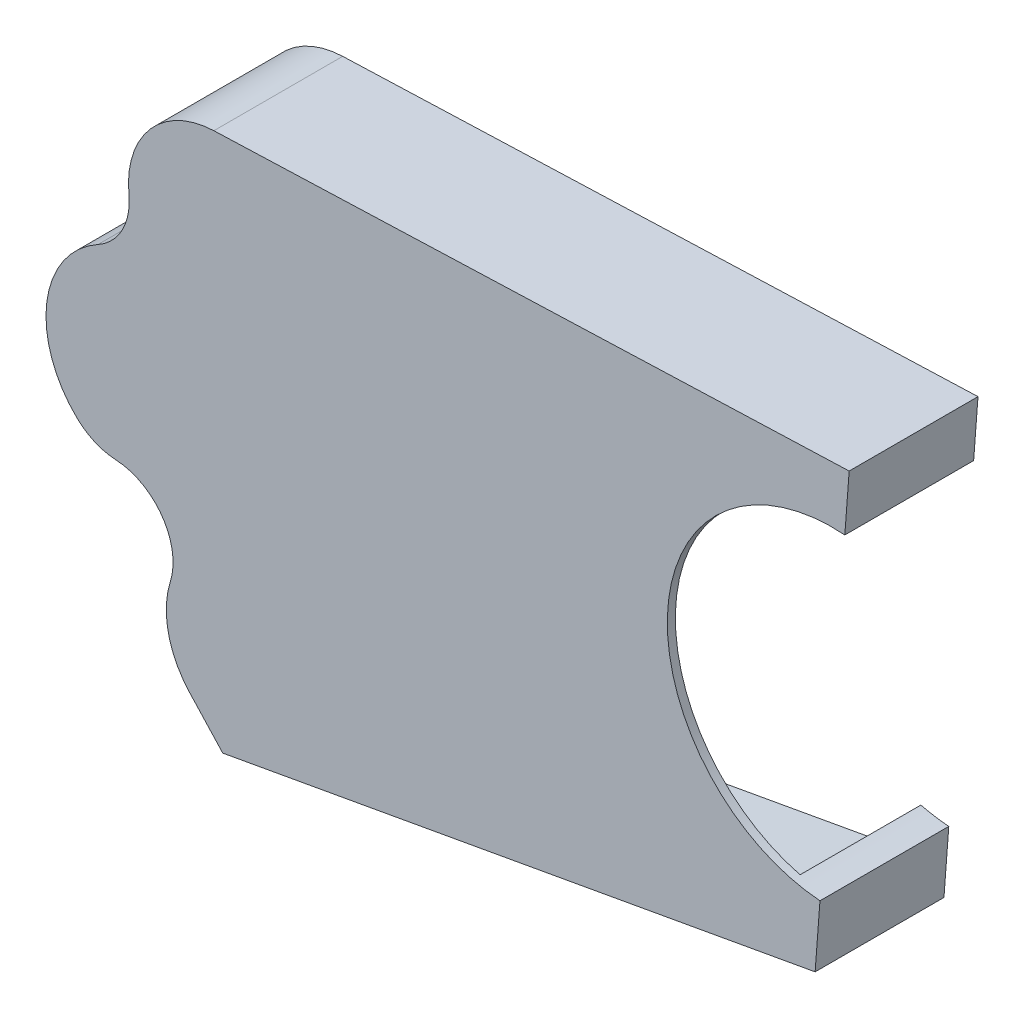
SolidWorks part; units mm, degrees
ref_plane "Front Plane" through (0, 0, 0) normal (0, 0, 1) x (1, 0, 0)
ref_plane "Top Plane" through (0, 0, 0) normal (0, 1, 0) x (1, 0, 0)
ref_plane "Right Plane" through (0, 0, 0) normal (1, 0, 0) x (0, 0, -1)
sketch "Sketch1" plane through (0, 0, 0) normal (0, 0, 1) x (1, 0, 0)
  line L8 (-119.5948, -74.4106) -> (-92.5405, -103.7404)
  line L9 (-119.5948, -74.4106) -> (-92.5405, -103.7404)
  line L10 (-71.3446, -104.5958) -> (-37.2211, -73.1197)
  line L11 (-71.3446, -104.5958) -> (-37.2211, -73.1197)
  line L16 (-27.1401, -68.1042) -> (68.9251, -50.7959)
  line L17 (-111.4072, -83.2869) -> (68.9251, -50.7959)
  line L18 (56.0883, 55.6165) -> (-113.6124, 49.4857)
  line L19 (56.0883, 55.6165) -> (-113.6124, 49.4857)
  line L20 (-114.4495, -69.6645) -> (-87.3952, -98.9943)
  line L21 (-114.4495, -69.6645) -> (-87.3952, -98.9943)
  line L22 (-76.0907, -99.4505) -> (-41.9673, -67.9744)
  line L23 (-76.0907, -99.4505) -> (-41.9673, -67.9744)
  line L28 (-28.3813, -61.2151) -> (67.6838, -43.9068)
  line L29 (-108.8671, -75.7165) -> (67.6838, -43.9068)
  line L30 (56.341, 48.621) -> (-113.3597, 42.4902)
  line L31 (56.341, 48.621) -> (-113.3597, 42.4902)
  line L32 (44.1846, 55.1864) -> (35.7309, -56.7765)
  line L33 (-27.1401, -68.1042) -> (68.9251, -50.7959) construction
  line L34 (-113.6124, 49.4857) -> (56.0883, 55.6165) construction
  line L35 (-111.6252, 43.3) -> (42.409, 31.6699) construction
  line L36 (36.6151, 47.9084) -> (29.1586, -50.848)
  arc A22 (-124.4228, -52.9336) -> (-137.9704, -33.4802) centre (-138.7403, -48.4604) ccw
  arc A23 (-124.4228, -52.9336) -> (-137.9704, -33.4802) centre (-138.7403, -48.4604) ccw
  arc A24 (-124.4228, -52.9336) -> (-119.5948, -74.4106) centre (-103.4238, -59.4942) ccw
  arc A25 (-124.4228, -52.9336) -> (-119.5948, -74.4106) centre (-103.4238, -59.4942) ccw
  arc A26 (-92.5405, -103.7404) -> (-71.3446, -104.5958) centre (-81.5148, -93.5701) ccw
  arc A27 (-92.5405, -103.7404) -> (-71.3446, -104.5958) centre (-81.5148, -93.5701) ccw
  arc A28 (-27.1401, -68.1042) -> (-37.2211, -73.1197) centre (-23.5699, -87.9191) ccw
  arc A29 (-27.1401, -68.1042) -> (-37.2211, -73.1197) centre (-23.5699, -87.9191) ccw
  arc A30 (68.9251, -50.7959) -> (91, -33.5) centre (63.6055, -21.2712) ccw
  arc A31 (68.9251, -50.7959) -> (91, -33.5) centre (63.6055, -21.2712) ccw
  arc A32 (91, -33.5) -> (80.2612, 44.7896) centre (22.6589, -2.9929) ccw
  arc A44 (91, -33.5) -> (80.2612, 44.7896) centre (22.6589, -2.9929) ccw
  arc A45 (80.2612, 44.7896) -> (56.0883, 55.6165) centre (57.1714, 25.636) ccw
  arc A46 (80.2612, 44.7896) -> (56.0883, 55.6165) centre (57.1714, 25.636) ccw
  arc A47 (-113.6124, 49.4857) -> (-134.7058, 25.2795) centre (-112.8181, 27.5) ccw
  arc A48 (-113.6124, 49.4857) -> (-134.7058, 25.2795) centre (-112.8181, 27.5) ccw
  arc A49 (-142.3827, 10.6321) -> (-134.7058, 25.2795) centre (-149.6292, 23.7656) ccw
  arc A50 (-142.3827, 10.6321) -> (-134.7058, 25.2795) centre (-149.6292, 23.7656) ccw
  arc A51 (-142.3827, 10.6321) -> (-147.5429, -29.3643) centre (-130.3054, -11.2571) ccw
  arc A52 (-142.3827, 10.6321) -> (-147.5429, -29.3643) centre (-130.3054, -11.2571) ccw
  arc A53 (-147.5429, -29.3643) -> (-137.9704, -33.4802) centre (-137.2004, -18.5) ccw
  arc A54 (-147.5429, -29.3643) -> (-137.9704, -33.4802) centre (-137.2004, -18.5) ccw
  arc A55 (-117.7413, -55.0211) -> (-137.611, -26.4895) centre (-138.7403, -48.4604) ccw
  arc A56 (-117.7413, -55.0211) -> (-137.611, -26.4895) centre (-138.7403, -48.4604) ccw
  arc A57 (-117.7413, -55.0211) -> (-114.4495, -69.6645) centre (-103.4238, -59.4942) ccw
  arc A58 (-117.7413, -55.0211) -> (-114.4495, -69.6645) centre (-103.4238, -59.4942) ccw
  arc A59 (-87.3952, -98.9943) -> (-76.0907, -99.4505) centre (-81.5148, -93.5701) ccw
  arc A60 (-87.3952, -98.9943) -> (-76.0907, -99.4505) centre (-81.5148, -93.5701) ccw
  arc A61 (-28.3813, -61.2151) -> (-41.9673, -67.9744) centre (-23.5699, -87.9191) ccw
  arc A62 (-28.3813, -61.2151) -> (-41.9673, -67.9744) centre (-23.5699, -87.9191) ccw
  arc A63 (67.6838, -43.9068) -> (84.608, -30.6466) centre (63.6055, -21.2712) ccw
  arc A73 (67.6838, -43.9068) -> (84.608, -30.6466) centre (63.6055, -21.2712) ccw
  arc A74 (84.608, -30.6466) -> (74.8736, 40.3204) centre (22.6589, -2.9929) ccw
  arc A75 (84.608, -30.6466) -> (74.8736, 40.3204) centre (22.6589, -2.9929) ccw
  arc A76 (74.8736, 40.3204) -> (56.341, 48.621) centre (57.1714, 25.636) ccw
  arc A77 (74.8736, 40.3204) -> (56.341, 48.621) centre (57.1714, 25.636) ccw
  arc A78 (-113.3597, 42.4902) -> (-127.7415, 25.986) centre (-112.8181, 27.5) ccw
  arc A79 (-113.3597, 42.4902) -> (-127.7415, 25.986) centre (-112.8181, 27.5) ccw
  arc A80 (-139.0011, 4.5031) -> (-127.7415, 25.986) centre (-149.6292, 23.7656) ccw
  arc A81 (-139.0011, 4.5031) -> (-127.7415, 25.986) centre (-149.6292, 23.7656) ccw
  arc A82 (-139.0011, 4.5031) -> (-142.7164, -24.2943) centre (-130.3054, -11.2571) ccw
  arc A83 (-139.0011, 4.5031) -> (-142.7164, -24.2943) centre (-130.3054, -11.2571) ccw
  arc A84 (-142.7164, -24.2943) -> (-137.611, -26.4895) centre (-137.2004, -18.5) ccw
  arc A85 (-142.7164, -24.2943) -> (-137.611, -26.4895) centre (-137.2004, -18.5) ccw
  circle A86 centre (40.0178, 0) radius 41
  arc A87 (29.9353, 38.7084) -> (0.6941, 7.3245) centre (40.0178, 0) ccw construction
  dimension "D4" = 1
  dimension "D3" = 7
  dimension "D1" = 0
  dimension "D2" = 7
extrude "Boss-Extrude1" add sketch "Sketch1" along normal blind 30 contours A52 A54 A23 A25 L9 A27 L11 A29 L17 A31 A44 A46 L19 A48 A50 A85 A83 A81 A79 L31 A77 A75 A73 L29 A62 L23 A60 L21 A58 A56 | A62 L29 L21 L17 L23 | L29 A62 L23 L17 L32 | A86 L36 L29 L32 | A86 L32 L31 L36 region at (-122.5189, -63.7868, 0) region at (-72.9993, -72.6407, 0) region at (-2.1687, -60.1476, 0) region at (32.9424, -45.3152, 0) region at (39.8821, 44.4918, 0)
sketch "Sketch3" plane through (0, 0, 30) normal (0, 0, 1) x (1, 0, 0)
  line L0 (-65.2656, 44.2277) -> (121.4688, -34.2162)
  line L1 (-113.3597, 42.4902) -> (36.6151, 47.9084) construction
  line L2 (29.1586, -50.848) -> (-108.8671, -75.7165) construction
  dimension "D1" = 33
sketch "Sketch4" plane through (0, 0, 30) normal (0, 0, 1) x (1, 0, 0)
  line L21 (-113.3597, 42.4902) -> (36.6151, 47.9084)
  line L22 (36.6151, 47.9084) -> (36.0792, 40.8104)
  line L23 (43.1047, 40.8836) -> (44.1846, 55.1864)
  line L24 (44.1846, 55.1864) -> (-113.6124, 49.4857)
  line L25 (-119.5948, -74.4106) -> (-111.4072, -83.2869)
  line L26 (-111.4072, -83.2869) -> (35.7309, -56.7765)
  line L27 (35.7309, -56.7765) -> (36.9309, -40.8836)
  line L28 (29.9961, -39.7563) -> (29.1586, -50.848)
  line L29 (29.1586, -50.848) -> (-108.8671, -75.7165)
  line L30 (-108.8671, -75.7165) -> (-114.4495, -69.6645)
  line L31 (-113.3597, 42.4902) -> (36.6151, 47.9084)
  line L32 (36.6151, 47.9084) -> (36.0792, 40.8104)
  line L33 (43.1047, 40.8836) -> (44.1846, 55.1864)
  line L34 (44.1846, 55.1864) -> (-113.6124, 49.4857)
  line L35 (-119.5948, -74.4106) -> (-111.4072, -83.2869)
  line L36 (-111.4072, -83.2869) -> (35.7309, -56.7765)
  line L37 (35.7309, -56.7765) -> (36.9309, -40.8836)
  line L38 (29.9961, -39.7563) -> (29.1586, -50.848)
  line L39 (29.1586, -50.848) -> (-108.8671, -75.7165)
  line L40 (-108.8671, -75.7165) -> (-114.4495, -69.6645)
  circle A14 centre (40.0178, 0) radius 41
  arc A28 (-142.7164, -24.2943) -> (-137.611, -26.4895) centre (-137.2004, -18.5) ccw
  arc A29 (-139.0011, 4.5031) -> (-142.7164, -24.2943) centre (-130.3054, -11.2571) ccw
  arc A30 (-139.0011, 4.5031) -> (-127.7415, 25.986) centre (-149.6292, 23.7656) ccw
  arc A31 (-113.3597, 42.4902) -> (-127.7415, 25.986) centre (-112.8181, 27.5) ccw
  arc A32 (43.1047, 40.8836) -> (36.0792, 40.8104) centre (40.0178, 0) ccw
  arc A33 (-113.6124, 49.4857) -> (-134.7058, 25.2795) centre (-112.8181, 27.5) ccw
  arc A34 (-142.3827, 10.6321) -> (-134.7058, 25.2795) centre (-149.6292, 23.7656) ccw
  arc A35 (-142.3827, 10.6321) -> (-147.5429, -29.3643) centre (-130.3054, -11.2571) ccw
  arc A36 (-147.5429, -29.3643) -> (-137.9704, -33.4802) centre (-137.2004, -18.5) ccw
  arc A37 (-124.4228, -52.9336) -> (-137.9704, -33.4802) centre (-138.7403, -48.4604) ccw
  arc A38 (-124.4228, -52.9336) -> (-119.5948, -74.4106) centre (-103.4238, -59.4942) ccw
  arc A39 (29.9961, -39.7563) -> (36.9309, -40.8836) centre (40.0178, 0) ccw
  arc A40 (-117.7413, -55.0211) -> (-114.4495, -69.6645) centre (-103.4238, -59.4942) ccw
  arc A41 (-117.7413, -55.0211) -> (-137.611, -26.4895) centre (-138.7403, -48.4604) ccw
  arc A42 (-142.7164, -24.2943) -> (-137.611, -26.4895) centre (-137.2004, -18.5) ccw
  arc A43 (-139.0011, 4.5031) -> (-142.7164, -24.2943) centre (-130.3054, -11.2571) ccw
  arc A44 (-139.0011, 4.5031) -> (-127.7415, 25.986) centre (-149.6292, 23.7656) ccw
  arc A45 (-113.3597, 42.4902) -> (-127.7415, 25.986) centre (-112.8181, 27.5) ccw
  arc A46 (43.1047, 40.8836) -> (36.0792, 40.8104) centre (40.0178, 0) ccw
  arc A47 (-113.6124, 49.4857) -> (-134.7058, 25.2795) centre (-112.8181, 27.5) ccw
  arc A48 (-142.3827, 10.6321) -> (-134.7058, 25.2795) centre (-149.6292, 23.7656) ccw
  arc A49 (-142.3827, 10.6321) -> (-147.5429, -29.3643) centre (-130.3054, -11.2571) ccw
  arc A50 (-147.5429, -29.3643) -> (-137.9704, -33.4802) centre (-137.2004, -18.5) ccw
  arc A51 (-124.4228, -52.9336) -> (-137.9704, -33.4802) centre (-138.7403, -48.4604) ccw
  arc A52 (-124.4228, -52.9336) -> (-119.5948, -74.4106) centre (-103.4238, -59.4942) ccw
  arc A53 (29.9961, -39.7563) -> (36.9309, -40.8836) centre (40.0178, 0) ccw
  arc A54 (-117.7413, -55.0211) -> (-114.4495, -69.6645) centre (-103.4238, -59.4942) ccw
  arc A55 (-117.7413, -55.0211) -> (-137.611, -26.4895) centre (-138.7403, -48.4604) ccw
  arc M25 (-137.611, -26.4895) -> (-142.7164, -24.2943) centre (-137.2004, -18.5) cw
  arc M26 (-142.7164, -24.2943) -> (-139.0011, 4.5031) centre (-130.3054, -11.2571) cw
  arc M27 (-139.0011, 4.5031) -> (-127.7415, 25.986) centre (-149.6292, 23.7656) ccw
  arc M28 (-127.7415, 25.986) -> (-113.3597, 42.4902) centre (-112.8181, 27.5) cw
  line M29 (-113.3597, 42.4902) -> (36.6151, 47.9084)
  line M30 (36.6151, 47.9084) -> (36.0792, 40.8104)
  arc M31 (36.0792, 40.8104) -> (43.1047, 40.8836) centre (40.0178, 0) cw
  line M32 (43.1047, 40.8836) -> (44.1846, 55.1864)
  line M33 (44.1846, 55.1864) -> (-113.6124, 49.4857)
  arc M34 (-113.6124, 49.4857) -> (-134.7058, 25.2795) centre (-112.8181, 27.5) ccw
  arc M35 (-134.7058, 25.2795) -> (-142.3827, 10.6321) centre (-149.6292, 23.7656) cw
  arc M36 (-142.3827, 10.6321) -> (-147.5429, -29.3643) centre (-130.3054, -11.2571) ccw
  arc M37 (-147.5429, -29.3643) -> (-137.9704, -33.4802) centre (-137.2004, -18.5) ccw
  arc M38 (-137.9704, -33.4802) -> (-124.4228, -52.9336) centre (-138.7403, -48.4604) cw
  arc M39 (-124.4228, -52.9336) -> (-119.5948, -74.4106) centre (-103.4238, -59.4942) ccw
  line M40 (-119.5948, -74.4106) -> (-111.4072, -83.2869)
  line M41 (-111.4072, -83.2869) -> (35.7309, -56.7765)
  line M42 (35.7309, -56.7765) -> (36.9309, -40.8836)
  arc M43 (36.9309, -40.8836) -> (29.9961, -39.7563) centre (40.0178, 0) cw
  line M44 (29.9961, -39.7563) -> (29.1586, -50.848)
  line M45 (29.1586, -50.848) -> (-108.8671, -75.7165)
  line M46 (-108.8671, -75.7165) -> (-114.4495, -69.6645)
  arc M47 (-114.4495, -69.6645) -> (-117.7413, -55.0211) centre (-103.4238, -59.4942) cw
  arc M48 (-117.7413, -55.0211) -> (-137.611, -26.4895) centre (-138.7403, -48.4604) ccw
  dimension "D1" = 0
extrude "Boss-Extrude2" add sketch "Sketch4" along normal blind 2 contours A14 M30 M29 M28 M27 M26 M25 M48 M47 M46 M45 M44 | M48 M25 M26 M27 M28 M29 M30 M31 M32 M33 M34 M35 M36 M37 M38 M39 M40 M41 M42 M43 M44 M45 M46 M47 region at (-125.9577, 38.9499, 30) region at (-60.3524, -9.964, 30)
